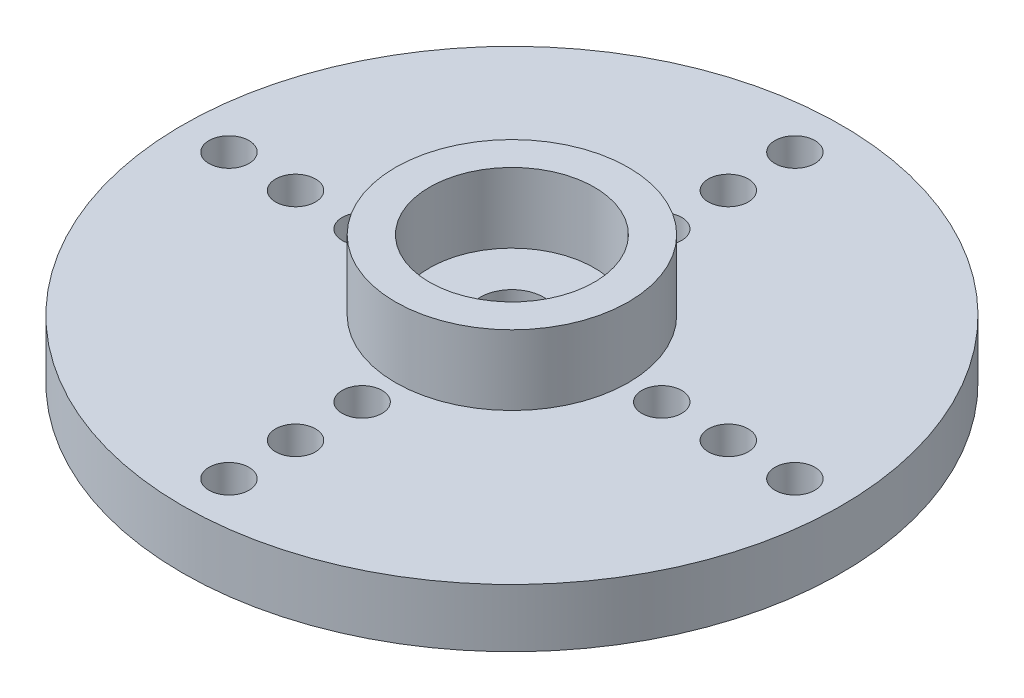
SolidWorks part; units mm, degrees
ref_plane "Plan de face" through (0, 0, 0) normal (0, 0, 1) x (1, 0, 0)
ref_plane "Plan de dessus" through (0, 0, 0) normal (0, 1, 0) x (1, 0, 0)
ref_plane "Plan de droite" through (0, 0, 0) normal (1, 0, 0) x (0, 0, -1)
sketch "Esquisse1" plane through (0, 0, 0) normal (0, 1, 0) x (1, 0, 0)
  circle A0 centre (0, 0) radius 9.9
  dimension "D1" = 19.8
extrude "Boss.-Extru.1" add sketch "Esquisse1" along normal blind 1.75
sketch "Esquisse2" plane through (0, 1.75, 0) normal (0, 1, 0) x (1, 0, 0)
  circle A0 centre (0, 0) radius 3.5
  circle A1 centre (0, 0) radius 2.475
  dimension "D1" = 7
  dimension "D2" = 4.95
extrude "Boss.-Extru.2" add sketch "Esquisse2" along normal blind 2.1
sketch "Esquisse3" plane through (0, 0, 0) normal (0, -1, 0) x (1, 0, 0)
  circle A0 centre (0, 0) radius 2.725
  circle A1 centre (0, 0) radius 2.225
  dimension "D1" = 5.45
  dimension "D2" = 0.5
extrude "Boss.-Extru.3" add sketch "Esquisse3" along normal blind 0.3
sketch "Esquisse4" plane through (0, 0, 0) normal (0, -1, 0) x (1, 0, 0)
  circle A0 centre (0, 0) radius 0.95
  dimension "D1" = 1.9
extrude "Enlèv. mat.-Extru.1" cut sketch "Esquisse4" against normal through all
sketch "Esquisse5" plane through (0, 0, 0) normal (0, -1, 0) x (1, 0, 0)
  line L0 (0, 0) -> (0, 9.9) construction
  circle A1 centre (0, 0) radius 9.9 construction
  circle A2 centre (0, 4.5) radius 0.6
  circle A3 centre (0, 6.5) radius 0.6
  circle A4 centre (0, 8.5) radius 0.6
  dimension "D4" = 1.2
  dimension "D1" = 2
  dimension "D2" = 2
  dimension "D3" = 4.5
extrude "Enlèv. mat.-Extru.2" cut sketch "Esquisse5" against normal through all
pattern_circular "Répétition circulaire1" count 4 over 360 about axis through (0, 1.75, 0) along (0, -1, 0) of "Enlèv. mat.-Extru.2"
